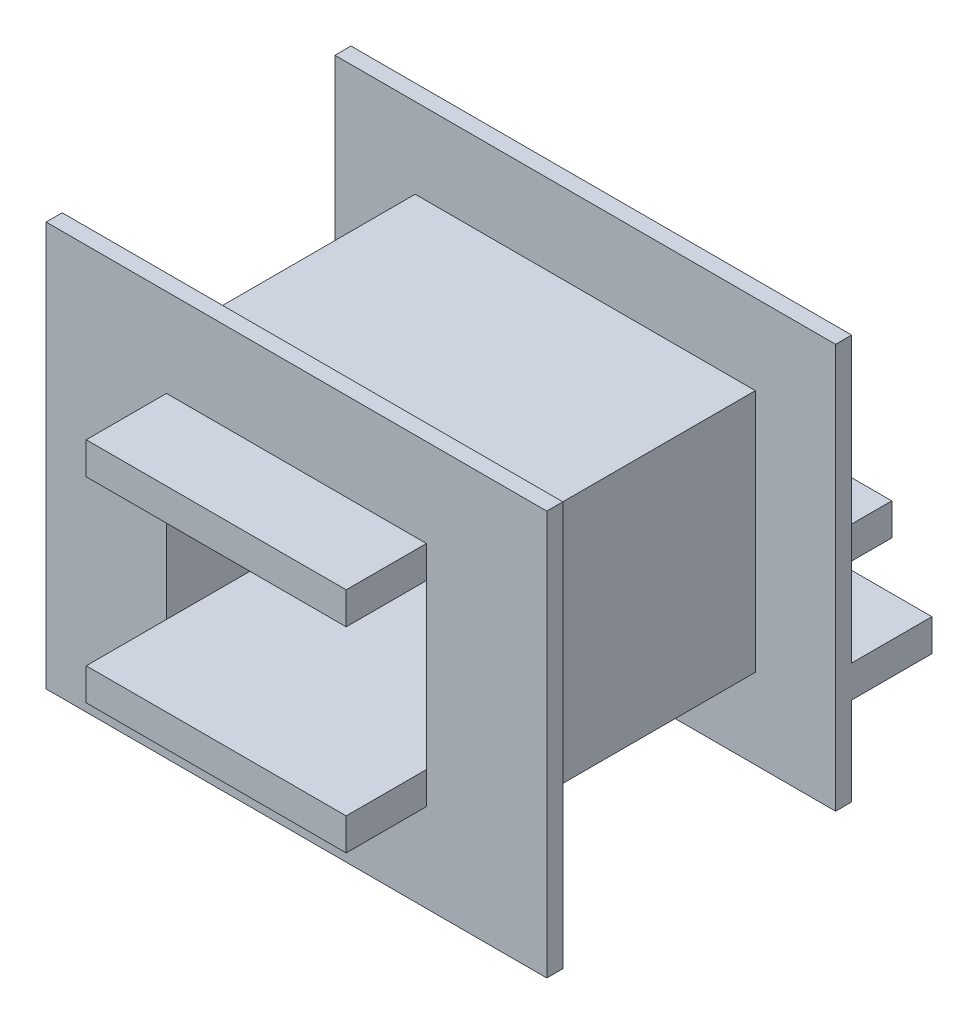
SolidWorks part; units mm, degrees
material "Nylon 101"
ref_plane "Front Plane" through (0, 0, 0) normal (0, 0, 1) x (1, 0, 0)
ref_plane "Top Plane" through (0, 0, 0) normal (0, 1, 0) x (1, 0, 0)
ref_plane "Right Plane" through (0, 0, 0) normal (1, 0, 0) x (0, 0, -1)
sketch "Sketch1" plane through (0, 0, 0) normal (0, 0, 1) x (1, 0, 0)
  line L0 (-8.1, -5.1) -> (8.1, 5.1) construction
  line L4 (-15.6, -12.6) -> (15.6, -12.6)
  line L5 (15.6, -12.6) -> (15.6, 12.6)
  line L6 (15.6, 12.6) -> (-15.6, 12.6)
  line L7 (-15.6, 12.6) -> (-15.6, -12.6)
  line L12 (-8.1, -5.1) -> (8.1, -5.1)
  line L13 (8.1, -5.1) -> (8.1, 5.1)
  line L14 (8.1, 5.1) -> (-8.1, 5.1)
  line L15 (-8.1, 5.1) -> (-8.1, -5.1)
  point P8 (0, 0)
  dimension "D1" = 10.2
  dimension "D3" = 16.2
  dimension "D2" = 7.5
extrude "Boss-Extrude1" add sketch "Sketch1" along normal blind 9.5 and the other way blind 9.5
sketch "Sketch2" plane through (0, 12.6, 0) normal (0, 1, 0) x (1, 0, 0)
  line L0 (-15.6, 9.5) -> (-15.6, -9.5) construction
  line L1 (-15.6, 8.5) -> (15.6, 8.5)
  line L2 (-15.6, 8.5) -> (-15.6, -8.5)
  line L3 (-15.6, -8.5) -> (15.6, -8.5)
  line L4 (15.6, 8.5) -> (15.6, -8.5)
  line L5 (15.6, 9.5) -> (15.6, -9.5) construction
  line L6 (15.6, 8.5) -> (-15.6, -8.5) construction
  line L7 (15.6, 9.5) -> (-15.6, 9.5) construction
  dimension "D1" = 1
extrude "Cut-Extrude1" cut sketch "Sketch2" against normal blind 5
mirror "Mirror1" about plane through (0, 0, 0) normal (0, 1, 0) of "Cut-Extrude1"
sketch "Sketch3" plane through (15.6, 0, 0) normal (1, 0, 0) x (0, 0, -1)
  line L1 (-8.5, 7.6) -> (8.5, 7.6)
  line L2 (-8.5, 7.6) -> (-8.5, -7.6)
  line L3 (-8.5, -7.6) -> (8.5, -7.6)
  line L4 (8.5, 7.6) -> (8.5, -7.6)
extrude "Cut-Extrude2" cut sketch "Sketch3" against normal blind 5
mirror "Mirror2" about plane through (0, 0, 0) normal (1, 0, 0) of "Cut-Extrude2"
sketch "Sketch4" plane through (0, 0, 9.5) normal (0, 0, 1) x (1, 0, 0)
  line L1 (-8.1, 5.1) -> (8.1, 5.1)
  line L2 (-8.1, 5.1) -> (-8.1, 7.1)
  line L3 (-8.1, 7.1) -> (8.1, 7.1)
  line L4 (8.1, 5.1) -> (8.1, 7.1)
  line L5 (8.1, -5.1) -> (-8.1, -5.1)
  line L6 (8.1, -5.1) -> (8.1, -7.1)
  line L7 (8.1, -7.1) -> (-8.1, -7.1)
  line L8 (-8.1, -5.1) -> (-8.1, -7.1)
  dimension "D1" = 2
extrude "Boss-Extrude2" add sketch "Sketch4" along normal blind 5
mirror "Mirror3" about plane through (0, 0, 0) normal (0, 0, 1) of "Boss-Extrude2"
sketch "Sketch5" plane through (0, -5.1, 0) normal (0, 1, 0) x (1, 0, 0)
  line L0 (8.1, -14.5) -> (8.1, -9.5) construction
  line L1 (-8.1, 19.5) -> (8.1, 19.5)
  line L2 (-8.1, 19.5) -> (-8.1, 14.5)
  line L3 (8.1, 14.5) -> (-8.1, 14.5) construction
  line L4 (8.1, 19.5) -> (8.1, 14.5)
  line L6 (-26.1, 14.5) -> (25.9, 14.5) construction
  line L7 (-8.1, 9.5) -> (-15.6, 9.5)
  line L8 (-8.1, 14.5) -> (-8.1, 9.5) construction
  line L9 (-8.1, 14.5) -> (-15.6, 14.5)
  line L10 (-15.6, 9.5) -> (-15.6, 14.5)
  line L11 (-15.6, 9.5) -> (-15.6, 8.5) construction
  line L12 (8.1, 14.5) -> (15.6, 14.5)
  line L14 (8.1, 9.5) -> (15.6, 9.5)
  line L15 (15.6, 14.5) -> (15.6, 9.5)
  line L16 (-8.1, 9.5) -> (8.1, 9.5)
  line L17 (8.1, 14.5) -> (8.1, 9.5) construction
  dimension "D1" = 5
extrude "Boss-Extrude3" add sketch "Sketch5" against normal blind 2
sketch "Sketch6" plane through (0, 7.1, 0) normal (0, 1, 0) x (1, 0, 0)
  line L1 (-8.1, 14.5) -> (8.1, 14.5)
  line L2 (-8.1, 14.5) -> (-8.1, 9.5)
  line L3 (-8.1, 9.5) -> (8.1, 9.5)
  line L4 (8.1, 14.5) -> (8.1, 9.5)
extrude "Cut-Extrude3" cut sketch "Sketch6" against normal blind 2
